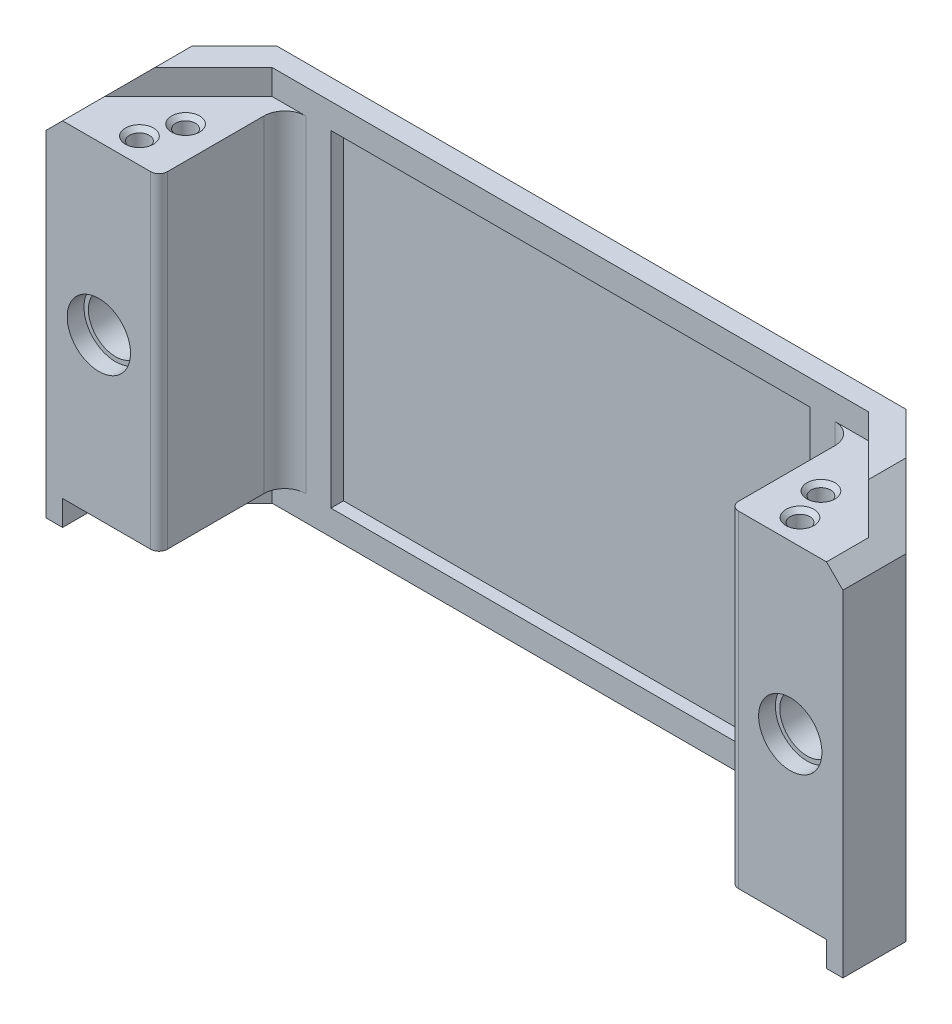
SolidWorks part; units mm, degrees
ref_plane "Front Plane" through (0, 0, 0) normal (0, 0, 1) x (1, 0, 0)
ref_plane "Top Plane" through (0, 0, 0) normal (0, 1, 0) x (1, 0, 0)
ref_plane "Right Plane" through (0, 0, 0) normal (1, 0, 0) x (0, 0, -1)
sketch "Sketch1" plane through (0, 0, 0) normal (0, 0, 1) x (1, 0, 0)
  line L1 (-95, 45) -> (95, 45)
  line L2 (-95, 45) -> (-95, -45)
  line L3 (-95, -45) -> (95, -45)
  line L4 (95, 45) -> (95, -45)
  line L5 (-95, 45) -> (95, -45) construction
  line L6 (-95, -45) -> (95, 45) construction
  point P0 (0, 0)
  point P6 (0, 0)
  dimension "D2" = 190
  dimension "D4" = 90
extrude "Boss-Extrude1" add sketch "Sketch1" along normal blind 5
sketch "Sketch2" plane through (0, 0, 5) normal (0, 0, 1) x (1, 0, 0)
  line L0 (-95, -45) -> (95, -45) construction
  line L1 (-95, 45) -> (-91.1, 45)
  line L2 (-95, 45) -> (-95, -45)
  line L3 (-95, -45) -> (-91.1, -45)
  line L4 (-91.1, 45) -> (-91.1, -45)
  line L5 (0, 0) -> (0, 45) construction
  line L6 (95, 45) -> (-95, 45) construction
  line L7 (95, -45) -> (91.1, -45)
  line L8 (91.1, 45) -> (91.1, -45)
  line L9 (95, 45) -> (91.1, 45)
  line L10 (95, 45) -> (95, -45)
  dimension "D1" = 3.9
extrude "Boss-Extrude2" add sketch "Sketch2" along normal blind 30
sketch "Sketch3" plane through (0, 45, 0) normal (0, 1, 0) x (1, 0, 0)
  line L0 (-91.1, -35) -> (-91.1, -5) construction
  line L1 (-91.1, -14) -> (-57.1, -14)
  line L2 (-91.1, -14) -> (-91.1, -19)
  line L3 (-91.1, -19) -> (-57.1, -19)
  line L4 (-57.1, -14) -> (-57.1, -19)
  line L5 (91.1, -35) -> (91.1, -5) construction
  line L6 (91.1, -14) -> (44.1, -14)
  line L7 (91.1, -14) -> (91.1, -19)
  line L8 (91.1, -19) -> (44.1, -19)
  line L9 (44.1, -14) -> (44.1, -19)
  line L10 (91.1, -5) -> (-91.1, -5) construction
  dimension "D1" = 9
  dimension "D2" = 9
  dimension "D3" = 5
  dimension "D4" = 5
  dimension "D5" = 34
  dimension "D6" = 47
extrude "Boss-Extrude3" add sketch "Sketch3" against normal up to surface (90 mm away) up to face at (0, -45, 18.75)
sketch "Sketch4" plane through (0, 0, 19) normal (0, 0, 1) x (1, 0, 0)
  line L0 (91.1, -45) -> (91.1, 45) construction
  line L1 (-91.1, 45) -> (91.1, 45)
  line L2 (-91.1, 45) -> (-91.1, 39)
  line L3 (-91.1, 39) -> (91.1, 39)
  line L4 (91.1, 45) -> (91.1, 39)
  line L5 (0, 0) -> (-91.1, 0) construction
  line L6 (-91.1, -45) -> (-91.1, 45) construction
  line L7 (-91.1, -39) -> (91.1, -39)
  line L8 (91.1, -45) -> (91.1, -39)
  line L9 (-91.1, -45) -> (91.1, -45)
  line L10 (-91.1, -45) -> (-91.1, -39)
  dimension "D1" = 6
extrude "Cut-Extrude1" cut sketch "Sketch4" against normal blind 5
chamfer "Chamfer6" distance 20 angle 45 4 edges at (91.1, 0, 5) (95, 0, 0) (-95, 0, 0) (-91.1, 0, 5)
sketch "Sketch7" plane through (0, 39, 0) normal (0, 1, 0) x (1, 0, 0)
  line L0 (-85.1, -19) -> (-91.1, -25)
  line L1 (-91.1, -25) -> (-91.1, -35)
  line L2 (-91.1, -35) -> (-68.1, -35)
  line L3 (-68.1, -35) -> (-68.1, -19)
  line L4 (-85.1, -19) -> (-57.1, -19) construction
  line L5 (-68.1, -19) -> (-85.1, -19)
  line L6 (0, 0) -> (0, -5) construction
  line L7 (71.1, -5) -> (-71.1, -5) construction
  line L8 (68.1, -35) -> (68.1, -19)
  line L9 (91.1, -35) -> (68.1, -35)
  line L10 (91.1, -25) -> (91.1, -35)
  line L11 (85.1, -19) -> (91.1, -25)
  line L12 (68.1, -19) -> (85.1, -19)
  dimension "D1" = 23
extrude "Boss-Extrude4" add sketch "Sketch7" against normal up to surface (78 mm away) up to face at (-69.85, -39, 16.5)
fillet "Fillet5" radius 2 2 edges at (-68.1, 0, 35) (68.1, 0, 35)
sketch "Sketch9" plane through (0, 0, 35) normal (0, 0, 1) x (1, 0, 0)
  line L6 (0, 0) -> (0, -45) construction
  line L7 (-71.1, -45) -> (71.1, -45) construction
  line L8 (-95, 45) -> (-95, -45) construction
  line L9 (-95, 39) -> (-82.45, 39) construction
  line L10 (-95, 39) -> (-95, -0.9074) construction
  line L11 (-95, -0.9074) -> (-82.45, -0.9074) construction
  line L12 (-82.45, 39) -> (-82.45, -0.9074) construction
  line L13 (-91.1, 39) -> (-70.1, 39) construction
  circle A0 centre (-82.45, -0.9074) radius 6.5
  circle A1 centre (82.45, -0.9074) radius 6.5
  dimension "D3" = 13
  dimension "D1" = 39.9074
  dimension "D2" = 12.55
extrude "Cut-Extrude4" cut sketch "Sketch9" against normal blind 10
sketch "Sketch10" plane through (0, 0, 35) normal (0, 0, 1) x (1, 0, 0)
  circle A0 centre (-82.45, -0.9074) radius 7.55
  circle A1 centre (82.45, -0.9074) radius 7.55
  dimension "D1" = 15.1
  dimension "D2" = 15.1
extrude "Cut-Extrude5" cut sketch "Sketch10" against normal blind 4
sketch "Sketch15" plane through (0, 39, 0) normal (0, 1, 0) x (1, 0, 0)
  line L0 (68.1, -19) -> (68.1, -33) construction
  line L5 (80.1, -14) -> (44.1, -14) construction
  line L6 (91.1, -35) -> (68.1, -35) construction
  line L7 (91.1, -35) -> (91.1, -14) construction
  line L8 (91.1, -14) -> (68.1, -14) construction
  line L9 (68.1, -35) -> (68.1, -14) construction
  line L10 (68.1, -14) -> (75.7667, -21) construction
  line L11 (75.7667, -21) -> (83.4333, -28) construction
  line L12 (83.4333, -28) -> (91.1, -35) construction
  line L13 (0, 0) -> (0, -5) construction
  line L14 (71.1, -5) -> (-71.1, -5) construction
  line L15 (75.7667, -21) -> (75.7667, -29) construction
  line L16 (75.7667, -29) -> (78.7667, -29) construction
  circle A0 centre (75.7667, -21) radius 2.35
  circle A1 centre (83.4333, -28) radius 2.35 construction
  circle A2 centre (-75.7667, -21) radius 2.35
  circle A3 centre (-83.4333, -28) radius 2.35 construction
  circle A6 centre (78.7667, -29) radius 2.35
  circle A7 centre (-78.7667, -29) radius 2.35
  dimension "D1" = 4.7
  dimension "D2" = 4.7
  dimension "D5" = 4.7
  dimension "D3" = 23
  dimension "D4" = 21
  dimension "D6" = 8
  dimension "D7" = 3
extrude "Cut-Extrude7" cut sketch "Sketch15" against normal blind 8
chamfer "Chamfer7" distance 1 angle 45 4 edges at (-75.7667, 39, 18.65) (75.7667, 39, 23.35) (-78.7667, 39, 26.65) (78.7667, 39, 31.35)
sketch "Sketch17" plane through (0, -39, 0) normal (0, -1, 0) x (1, 0, 0)
  line L0 (0, 0) -> (0, 5) construction
  line L1 (91.1, 35) -> (68.1, 35) construction
  line L2 (91.1, 35) -> (91.1, 19) construction
  line L3 (91.1, 19) -> (68.1, 19) construction
  line L4 (68.1, 35) -> (68.1, 19) construction
  line L5 (-71.1, 5) -> (71.1, 5) construction
  line L6 (68.1, 33) -> (68.1, 19) construction
  line L7 (68.1, 19) -> (44.1, 19) construction
  circle A0 centre (79.6, 27) radius 6.1
  circle A1 centre (-79.6, 27) radius 6.1
  dimension "D2" = 12.2
  dimension "D1" = 11.5
  dimension "D3" = 8
  dimension "D4" = 11.5
extrude "Cut-Extrude8" cut sketch "Sketch17" against normal blind 3.2
fillet "Fillet7" radius 0.2 2 edges at (-85.7, -39, 27) (85.7, -39, 27)
chamfer "Chamfer8" distance 9.9 angle 45 2 edges at (-95, 45, 27.5) (95, 45, 27.5)
sketch "Sketch18" plane through (-57.1, 0, 0) normal (1, 0, 0) x (0, 0, -1)
  line L1 (-19, 39) -> (-14, 39)
  line L2 (-19, 39) -> (-19, -39)
  line L3 (-19, -39) -> (-14, -39)
  line L4 (-14, 39) -> (-14, -39)
extrude "Cut-Extrude9" cut sketch "Sketch18" against normal up to surface and the other way up to surface up to face at (-68.1, 0, 26) other way up to face at (68.1, 0, 26)
sketch "Sketch20" plane through (0, 39, 0) normal (0, 1, 0) x (1, 0, 0)
  line L0 (-68.1, -14) -> (-68.1, -5)
  line L1 (71.1, -5) -> (-71.1, -5) construction
  line L2 (-68.1, -5) -> (-71.1, -5)
  line L3 (-71.1, -5) -> (-80.1, -14)
  line L4 (-80.1, -14) -> (-68.1, -14)
  line L5 (0, 0) -> (0, -5) construction
  line L6 (71.1, -5) -> (80.1, -14)
  line L7 (68.1, -5) -> (71.1, -5)
  line L8 (68.1, -14) -> (68.1, -5)
  line L9 (80.1, -14) -> (68.1, -14)
extrude "Boss-Extrude5" add sketch "Sketch20" against normal up to surface (78 mm away) up to face at (-85.9, -39, 27)
fillet "Fillet8" radius 5 2 edges at (68.1, 0, 5) (-68.1, 0, 5)
sketch "Sketch21" plane through (0, 0, 5) normal (0, 0, 1) x (1, 0, 0)
  line L0 (-71.1, -45) -> (71.1, -45) construction
  line L1 (-57.1, 39) -> (57.1, 39)
  line L2 (-57.1, 39) -> (-57.1, -39)
  line L3 (-57.1, -39) -> (57.1, -39)
  line L4 (57.1, 39) -> (57.1, -39)
  line L5 (71.1, 45) -> (-71.1, 45) construction
  line L6 (-63.1, 39) -> (-63.1, -39) construction
  line L7 (63.1, -39) -> (63.1, 39) construction
  dimension "D1" = 6
  dimension "D2" = 6
  dimension "D3" = 6
  dimension "D4" = 6
extrude "Cut-Extrude10" cut sketch "Sketch21" against normal blind 3
